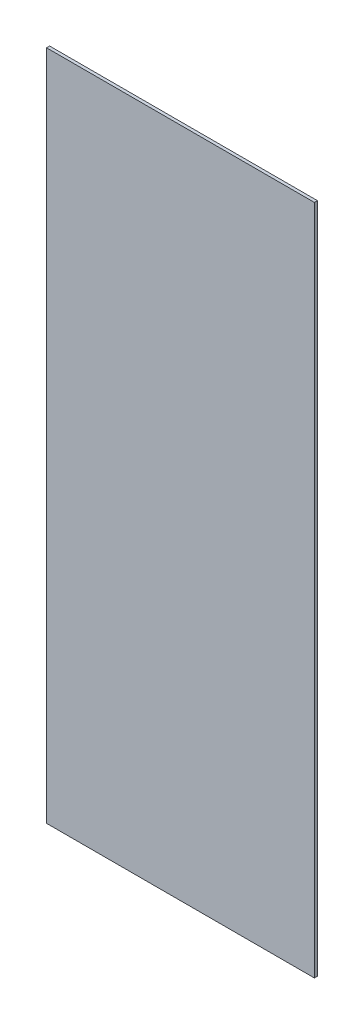
SolidWorks part; units mm, degrees
ref_plane "Спереди" through (0, 0, 0) normal (0, 0, 1) x (1, 0, 0)
ref_plane "Сверху" through (0, 0, 0) normal (0, 1, 0) x (1, 0, 0)
ref_plane "Справа" through (0, 0, 0) normal (1, 0, 0) x (0, 0, -1)
other "Configuration Table"
sketch "Эскиз1" plane through (0, 0, 0) normal (0, 0, 1) x (1, 0, 0)
  line L0 (0, -15) -> (0, -445) construction
  line L1 (524, 431) -> (0, 431)
  line L2 (524, 431) -> (524, -883)
  line L3 (524, -883) -> (0, -883)
  line L4 (0, 431) -> (0, -883)
  line L5 (524, 425) -> (524, -5) construction
  line L6 (0, 431) -> (518, 431) construction
  line L10 (518, -877) -> (524, -877) construction
  dimension "D1" = 6
extrude "Бобышка-Вытянуть1" add sketch "Эскиз1" against normal blind 6
equation "\"Толщина стенки\" = 6"
equation "\"D1@Эскиз1\"=\"Толщина стенки\""
equation "\"Ширина груза\"= 420"
equation "\"Глубина груза\"= 490"
equation "\"Высота груза\"= 297"
equation "\"Ширина ячейки\"= \"Ширина груза\" + 10"
equation "\"Глубина ячейки\"= \"Глубина груза\" + 10"
equation "\"Высота ячейки\"= \"Высота груза\" + 10 + 13"
equation "\"Колво ячеек ширина\"= 2"
equation "\"Колво ячеек высота\"= 2"
equation "\"Крепление дверцы\"= 5"
equation "\"Ширина рейки\"= \"Толщина шестерни\""
equation "\"Высота рейки\"= 20"
equation "\"Высота пола\"= 20"
equation "\"Колво полозьев\"= 5"
equation "\"Отступ рейки\"= 20"
equation "\"Глубина каретки\"= \"Глубина ячейки\" + 30 + \"Мотор Y высота корпуса\" + 20"
equation "\"Длинна рейки\"= ( \"Ширина ячейки\" + \"Толщина стенки\" + \"Крепление дверцы\" ) * \"Колво ячеек ширина\" + \"Ширина ячейки выгрузки\" * \"Колво выгрузки\" + \"Толщина стенки\""
equation "\"Отступ шпильки\"= 26"
equation "\"Диаметр шпильки\"= 5"
equation "\"Длинна шпильки\"= ( \"Высота ячейки\" + \"Толщина стенки\" + \"Высота пола\" ) * \"Колво ячеек высота\" + ( \"Толщина стенки\" + \"Отступ рейки\" ) * 2 "
equation "\"Ширина пластины\"= 50  "
equation "\"Высота зона выгрузки\"= \"Высота ячейки\" * 2 + \"Толщина стенки\" * 2"
equation "\"Колво выгрузки\"= 1"
equation "\"Ширина ячейки выгрузки\"= \"Ширина ячейки\" + \"Толщина стенки\" + \"Отступ крепления мотора фиксации\"*2"
equation "\"Отступ крепления мотора фиксации\" = 30"
equation "\"Мотор X ширина корпуса\"= 42.3"
equation "\"Мотор X высота корпуса\"= 42.3"
equation "\"Мотор X длина корпуса\"= 40"
equation "\"Мотор X вылет вала\"= 19.8"
equation "\"Мотор Y ширина корпуса\"= 42.3"
equation "\"Мотор Y высота корпуса\"= 42.3"
equation "\"Мотор Y длина корпуса\"= 48"
equation "\"Мотор Y вылет вала\"= 30"
equation "\"Мотор Z ширина корпуса\"= 42"
equation "\"Мотор Z высота корпуса\"= 42"
equation "\"Мотор Z длина корпуса\"= 40"
equation "\"Мотор Z вылет вала\"= 23"
equation "\"Мотор диаметр вала ПРЕДВ\"= 5"
equation "\"Мотор шаг крепления ПРЕДВ\"= 31"
equation "\"Мотор диаметр отверстий ПРЕДВ\"= 3"
equation "\"Мотор глубина отверстий ПРЕДВ\"= 4.5"
equation "\"Мотор диаметр буртика ПРЕДВ\"= 22"
equation "\"Мотор высота буртика ПРЕДВ\"= 2"
equation "\"Мотор диаметр шкива ПРЕДВ\"= 16"
equation "\"Мотор длина шкива ПРЕДВ\"= 12"
equation "\"Мотор отступ шкива ПРЕДВ\"= 5"
equation "\"Мотор X шаг градусов\"= 1.8"
equation "\"Мотор Y шаг градусов\"= 1.8"
equation "\"Мотор Z шаг градусов\"= 1.8"
equation "\"Мотор Y диаметр ротора\"= 25.78"
equation "\"Толщина шестерни\"= 10"
equation "\"D1@Бобышка-Вытянуть1\"=\"Толщина стенки\""
